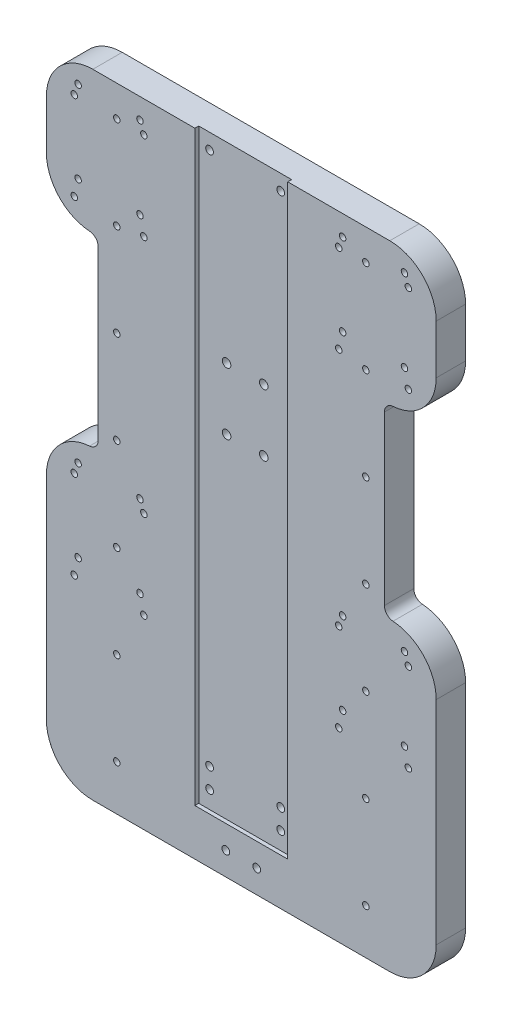
SolidWorks part; units mm, degrees
ref_plane "Piano frontale" through (0, 0, 0) normal (0, 0, 1) x (1, 0, 0)
ref_plane "Piano superiore" through (0, 0, 0) normal (0, 1, 0) x (1, 0, 0)
ref_plane "Piano destro" through (0, 0, 0) normal (1, 0, 0) x (0, 0, -1)
sketch "Schizzo1" plane through (0, 0, 0) normal (0, 0, 1) x (1, 0, 0)
  line L1 (126, -250) -> (-126, -250)
  line L2 (126, -250) -> (126, 250)
  line L3 (126, 250) -> (-126, 250)
  line L4 (-126, -250) -> (-126, 250)
  line L5 (126, -250) -> (-126, 250) construction
  line L6 (126, 250) -> (-126, -250) construction
  point P0 (0, 0)
  dimension "D1" = 252
  dimension "D2" = 500
extrude "Estrusione-Estrusione1" add sketch "Schizzo1" along normal blind 19
sketch "Schizzo2" plane through (0, 0, 19) normal (0, 0, 1) x (1, 0, 0)
  line L0 (1265.2426, 21.4119) -> (-695.7574, 21.4119) construction
  line L1 (1265.2426, 13.5541) -> (-695.7574, 13.5541) construction
  line L2 (1265.2426, 53.5541) -> (-695.7574, 53.5541) construction
  line L3 (1265.2426, 61.4119) -> (-695.7574, 61.4119) construction
  line L4 (-126, 250) -> (-126, -250)
  line L5 (-126, -250) -> (126, -250)
  line L6 (126, -250) -> (126, 250)
  line L7 (126, 250) -> (-126, 250)
  line L8 (-126, 250) -> (-126, -250) construction
  line L9 (-126, -250) -> (126, -250) construction
  line L10 (126, -250) -> (126, 250) construction
  line L11 (126, 250) -> (-126, 250) construction
  line L12 (1265.2426, 21.4119) -> (-695.7574, 21.4119) construction
  line L13 (1265.2426, 13.5541) -> (-695.7574, 13.5541) construction
  line L14 (1265.2426, 53.5541) -> (-695.7574, 53.5541) construction
  line L15 (1265.2426, 61.4119) -> (-695.7574, 61.4119) construction
  line L16 (126, -45.017) -> (-126, -45.017) construction
  line L17 (126, -25.017) -> (-126, -25.017) construction
  line L18 (126, -45.017) -> (-126, -45.017) construction
  line L19 (126, -25.017) -> (-126, -25.017) construction
  line L20 (-126, -45.017) -> (-126, -25.017) construction
  line L21 (126, -35.017) -> (-126, -35.017) construction
  line L22 (-126, -45.017) -> (126, -45.017) construction
  line L23 (-126, -45.017) -> (-126, -25.017) construction
  line L24 (-126, -25.017) -> (126, -25.017) construction
  line L25 (126, -45.017) -> (126, -25.017) construction
  circle A0 centre (110, 17.483) radius 3.9289
  circle A1 centre (110, 57.483) radius 3.9289
  circle A2 centre (-110, 17.483) radius 3.9289
  circle A3 centre (-110, 57.483) radius 3.9289
  circle A4 centre (110, -35.017) radius 3.5
  circle A5 centre (-110, -35.017) radius 3.5
  circle A6 centre (55, -35.017) radius 3.5
  circle A8 centre (-55, -35.017) radius 3.5
  circle A9 centre (20, -35.017) radius 3.5
  circle A10 centre (-20, -35.017) radius 3.5
  circle A11 centre (165, -35.017) radius 3.5 [skipped]
  dimension "D2" = 16
  dimension "D3" = 7.8579
  dimension "D4" = 16
  dimension "D5" = 7.8579
  dimension "D6" = 7
  dimension "D7" = 7
  dimension "D8" = 2
  dimension "D1" = 0
  dimension "D9" = 2
  dimension "D10" = 2
  dimension "D11" = 2
sketch "Schizzo3" plane through (0, 250, 0) normal (0, 1, 0) x (1, 0, 0)
  line L0 (126, -19) -> (-126, -19) construction
  line L1 (30, -16.5) -> (-30, -16.5)
  line L2 (30, -16.5) -> (30, -19)
  line L3 (30, -19) -> (-30, -19)
  line L4 (-30, -16.5) -> (-30, -19)
  line L5 (126, -19) -> (126, 0) construction
  line L6 (-126, -19) -> (-126, 0) construction
  line L7 (126, -19) -> (-126, -19) construction
  dimension "D1" = 2.5
  dimension "D2" = 96
  dimension "D3" = 96
extrude "Taglio-Estrusione1" cut sketch "Schizzo3" against normal through all
sketch "Schizzo4" plane through (0, 0, 16.5) normal (0, 0, 1) x (1, 0, 0)
  line L0 (30, -250) -> (30, 250) construction
  line L2 (30, 250) -> (-30, 250) construction
  line L3 (30, -250) -> (30, 250) construction
  line L6 (-30, 250) -> (-126, 250) construction
  line L7 (-30, -250) -> (-30, 250) construction
  point P11 (23, -118)
  point P14 (-23, -118)
  point P15 (-23, -105)
  point P16 (23, -105)
  point P17 (23, 240)
  point P18 (-23, 240)
  dimension "D1" = 46
  dimension "D2" = 13
  dimension "D3" = 13
  dimension "D4" = 46
  dimension "D5" = 7
  dimension "D6" = 345
  dimension "D7" = 10
  dimension "D8" = 46
  dimension "D9" = 7
  dimension "D10" = 10
  dimension "D11" = 7
  dimension "D12" = 7
sketch "Schizzo5" plane through (0, 0, 19) normal (0, 0, 1) x (1, 0, 0)
  point P4 (80.5006, 170)
  point P7 (80.5006, 110)
  point P16 (80.5006, 50)
  point P17 (80.5006, -10)
  point P18 (80.5006, -70)
  point P19 (80.5006, -130)
  point P20 (80.5006, 230)
hole_wizard "Tap Drill for M5 Tap2" positions "Sketch7" profile "Sketch8" hole size "M5" standard "ISO"
sketch "Sketch7" plane through (0, 0, 19) normal (0, 0, 1) x (1, 0, 0)
  point P0 (80.5006, -130)
  point P3 (80.5006, -70)
  point P7 (80.5006, -10)
  point P10 (80.5006, 50)
  point P13 (80.5006, 110)
  point P16 (80.5006, 170)
  point P19 (80.5006, 230)
sketch "Sketch8" plane through (80.5006, -130, 19) normal (1, 0, 0) x (0, -1, 0)
  line L0 (0, 0) -> (0, 37.8618)
  line L1 (0, 37.8618) -> (2.1, 36.6)
  line L2 (2.1, 36.6) -> (2.1, 0)
  line L5 (2.1, 0) -> (0, 0)
  line L10 (0, 37.8618) -> (-2.1, 36.6) construction
  line L11 (0, -6.35) -> (0, 107.95) construction
  dimension "Hole Dia." = 4.2
  dimension "Hole Depth" = 36.6
  dimension "Drill Angle" = 118
sketch "Schizzo6" plane through (0, 0, 19) normal (0, 0, 1) x (1, 0, 0)
  line L0 (126, -250) -> (126, 250) construction
  line L2 (126, 250) -> (30, 250) construction
  point P23 (108, 172.8083)
  point P26 (63, 172.8083)
  point P27 (63, 229.8083)
  point P28 (108, 229.8083)
  dimension "D1" = 45
  dimension "D2" = 45
  dimension "D3" = 57
  dimension "D4" = 57
  dimension "D5" = 18
  dimension "D6" = 20.1917
  dimension "D7" = 20.1917
  dimension "D8" = 18
hole_wizard "Tap Drill for M5 Tap1" positions "Sketch14" profile "Sketch15" hole size "M5" standard "ISO"
sketch "Sketch14" plane through (0, 0, 19) normal (0, 0, 1) x (1, 0, 0)
  line L1 (105.5, 183.8083) -> (65.5, 183.8083)
  line L2 (105.5, 183.8083) -> (105.5, 236.8083)
  line L3 (105.5, 236.8083) -> (65.5, 236.8083)
  line L4 (65.5, 183.8083) -> (65.5, 236.8083)
  line L6 (105.5, -28.1917) -> (65.5, -28.1917)
  line L7 (105.5, -28.1917) -> (105.5, 24.8083)
  line L8 (105.5, 24.8083) -> (65.5, 24.8083)
  line L9 (65.5, -28.1917) -> (65.5, 24.8083)
  line L10 (85.5, -28.1917) -> (85.5, 236.8083) construction
  line L12 (105.5, 210.3083) -> (65.5, 210.3083) construction
  line L14 (105.5, -1.6917) -> (65.5, -1.6917) construction
  line L16 (108, 172.8083) -> (63, 172.8083) construction
  line L18 (85.5, 256.2745) -> (85.5, -301.4126) construction
  point P0 (108, 172.8083)
  point P3 (108, 229.8083)
  point P6 (63, 229.8083)
  point P9 (63, 172.8083)
  point P12 (63, 17.8083)
  point P14 (63, -39.1917)
  point P16 (108, -39.1917)
  point P18 (108, 17.8083)
  point P19 (105.5, 236.8083)
  point P21 (65.5, 236.8083)
  point P23 (105.5, 183.8083)
  point P25 (65.5, 183.8083)
  point P99 (105.5, -28.1917)
  point P102 (65.5, -28.1917)
  point P105 (65.5, 24.8083)
  point P108 (105.5, 24.8083)
  point P138 (105.5, 183.8083)
  point P139 (65.5, 183.8083)
  point P140 (65.5, 236.8083)
  point P141 (105.5, 236.8083)
  point P142 (105.5, -28.1917)
  point P143 (65.5, -28.1917)
  point P144 (65.5, 24.8083)
  point P145 (105.5, 24.8083)
  dimension "D1" = 40
  dimension "D2" = 53
  dimension "D3" = 40
  dimension "D4" = 53
sketch "Sketch15" plane through (108, 172.8083, 19) normal (1, 0, 0) x (0, -1, 0)
  line L0 (0, 0) -> (0, 37.8618)
  line L1 (0, 37.8618) -> (2.1, 36.6)
  line L2 (2.1, 36.6) -> (2.1, 0)
  line L5 (2.1, 0) -> (0, 0)
  line L10 (0, 37.8618) -> (-2.1, 36.6) construction
  line L11 (0, -6.35) -> (0, 107.95) construction
  dimension "Hole Dia." = 4.2
  dimension "Hole Depth" = 36.6
  dimension "Drill Angle" = 118
hole_wizard "Tap Drill for M6 Tap4" positions "Sketch9" profile "Sketch10" hole size "M6" standard "ISO"
sketch "Sketch9" plane through (0, 0, 16.5) normal (0, 0, 1) x (1, 0, 0)
  point P0 (23, -118)
  point P3 (23, -105)
  point P6 (-23, -118)
  point P9 (-23, -105)
  point P12 (23, 240)
  point P15 (-23, 240)
sketch "Sketch10" plane through (23, -118, 16.5) normal (1, 0, 0) x (0, -1, 0)
  line L0 (0, 0) -> (0, 38.1022)
  line L1 (0, 38.1022) -> (2.5, 36.6)
  line L2 (2.5, 36.6) -> (2.5, 0)
  line L5 (2.5, 0) -> (0, 0)
  line L10 (0, 38.1022) -> (-2.5, 36.6) construction
  line L11 (0, -6.35) -> (0, 107.95) construction
  dimension "Hole Dia." = 5
  dimension "Hole Depth" = 36.6
  dimension "Drill Angle" = 118
sketch "Sketch11" plane through (0, 0, 16.5) normal (0, 0, 1) x (1, 0, 0)
  line L0 (0, -250) -> (0, 250) construction
  line L1 (30, -250) -> (-30, -250) construction
  line L2 (30, 250) -> (-30, 250) construction
ref_plane "Plane1" through (0, 0, 0) normal (-1, 0, 0) x (0, 0, 1)
mirror "Mirror1" about plane through (0, 0, 0) normal (-1, 0, 0) of "Tap Drill for M5 Tap2"
mirror "Mirror2" about plane through (0, 0, 0) normal (-1, 0, 0) of "Tap Drill for M5 Tap1"
sketch "Sketch16" plane through (0, 0, 0) normal (0, 0, -1) x (-1, 0, 0)
  line L0 (126, 250) -> (126, -250) construction
  line L1 (126, -317.9299) -> (-126, -317.9299)
  line L2 (126, -317.9299) -> (126, -159.25)
  line L3 (126, -159.25) -> (-126, -159.25)
  line L4 (-126, -317.9299) -> (-126, -159.25)
  line L5 (-126, -250) -> (-126, 250) construction
  line L9 (-12.9, -159.25) -> (25.2, -159.25) construction
extrude "Cut-Extrude1" cut sketch "Sketch16" against normal blind 28
sketch "Sketch26" plane through (0, 0, 16.5) normal (0, 0, 1) x (1, 0, 0)
  line L0 (30, -159.25) -> (30, 250) construction
  line L1 (-30, -159.25) -> (30, -159.25)
  line L2 (-30, -159.25) -> (-30, -129.25)
  line L3 (-30, -129.25) -> (30, -129.25)
  line L4 (30, -159.25) -> (30, -129.25)
  dimension "D1" = 30
extrude "Boss-Extrude1" add sketch "Sketch26" along normal up to surface (2.5 mm away) up to face at (-78, 45.375, 19)
hole_wizard "M5 Clearance Hole1" positions "Sketch17" profile "Sketch18" hole size "M5" standard "ISO" end condition through all
sketch "Sketch17" plane through (0, 0, 16.5) normal (0, 0, 1) x (1, 0, 0)
  line L0 (12, 86.3083) -> (-12, 126.3083) construction
  line L1 (-12, 126.3083) -> (-12, 86.3083) construction
  line L2 (-12, 86.3083) -> (12, 126.3083) construction
  line L3 (12, 126.3083) -> (12, 86.3083) construction
  line L4 (12, 86.3083) -> (-12, 86.3083) construction
  line L7 (-12, 126.3083) -> (12, 126.3083) construction
  point P0 (-12, 86.3083)
  point P2 (12, 86.3083)
  point P4 (12, 126.3083)
  point P6 (-12, 126.3083)
  dimension "D1" = 40
  dimension "D2" = 24
sketch "Sketch18" plane through (-12, 86.3083, 16.5) normal (1, 0, 0) x (0, -1, 0)
  line L0 (0, 0) -> (0, 16.5)
  line L1 (0, 16.5) -> (2.75, 16.5)
  line L2 (2.75, 16.5) -> (2.75, 0)
  line L5 (2.75, 0) -> (0, 0)
  line L11 (0, -6.35) -> (0, 107.95) construction
  dimension "Thru Hole Dia." = 5.5
  dimension "Thru Hole Depth" = 16.5
sketch "Sketch19" plane through (0, -195.45, 0) normal (0, -1, 0) x (-1, 0, 0)
  line L0 (0, -70.7) -> (0, 68.239) construction
  line L1 (126, -9.5) -> (-126, -9.5) construction
  line L2 (126, -19) -> (126, 0) construction
  line L3 (-126, -19) -> (-126, 0) construction
  line L5 (28.2, 0) -> (-28.2, 0) construction
  point P8 (20, -9.5)
  point P9 (-20, -9.5)
  point P12 (-20, 9.5)
  point P13 (20, 9.5)
  dimension "D1" = 20
hole_wizard "Tap Drill for M6 Tap2" positions "Sketch22" profile "Sketch23" hole size "M6" standard "ISO"
sketch "Sketch22" plane through (0, -159.25, 0) normal (0, -1, 0) x (-1, 0, 0)
  point P0 (20, -7.125)
  point P2 (-20, -7.125)
sketch "Sketch23" plane through (-20, -159.25, 7.125) normal (1, 0, 0) x (0, 0, -1)
  line L0 (0, 0) -> (0, 31.5022)
  line L1 (0, 31.5022) -> (2.5, 30)
  line L2 (2.5, 30) -> (2.5, 0)
  line L5 (2.5, 0) -> (0, 0)
  line L10 (0, 31.5022) -> (-2.5, 30) construction
  line L11 (0, -6.35) -> (0, 107.95) construction
  dimension "Hole Dia." = 5
  dimension "Hole Depth" = 30
  dimension "Drill Angle" = 118
hole_wizard "Tap Drill for M6 Tap3" positions "Sketch24" profile "Sketch25" hole size "M6" standard "ISO" end condition through all
sketch "Sketch24" plane through (0, 0, 0) normal (0, 0, -1) x (-1, 0, 0)
  point P0 (-10, -144.25)
  point P6 (10, -144.25)
sketch "Sketch25" plane through (10, -144.25, 0) normal (1, 0, 0) x (0, 1, 0)
  line L0 (0, 0) -> (0, 19)
  line L1 (0, 19) -> (2.5, 19)
  line L2 (2.5, 19) -> (2.5, 0)
  line L5 (2.5, 0) -> (0, 0)
  line L11 (0, -6.35) -> (0, 107.95) construction
  dimension "Thru Hole Dia." = 5
  dimension "Thru Hole Depth" = 19
sketch "Sketch27" plane through (0, 0, 19) normal (0, 0, 1) x (1, 0, 0)
  line L2 (-126, 38.082) -> (-126, 158.222)
  line L4 (-92.5, 38.082) -> (-92.5, 158.222)
  line L5 (-126, 38.082) -> (-92.5, 38.082)
  line L7 (-126, 158.222) -> (-92.5, 158.222)
  line L9 (-92.5, 40.082) -> (-92.5, 156.222) construction
  line L10 (-126, 40.082) -> (-126, 156.222) construction
  line L11 (-128, 158.222) -> (-90.5, 158.222) construction
  line L12 (-128, 38.082) -> (-128, 158.222) construction
  line L13 (-128, 38.082) -> (-90.5, 38.082) construction
  line L14 (-126, 40.082) -> (-92.5, 40.082) construction
  line L15 (-90.5, 38.082) -> (-90.5, 158.222) construction
  line L16 (-126, 156.222) -> (-92.5, 156.222) construction
  line L17 (-126, 98.152) -> (126, 98.152) construction
  line L18 (126, -159.25) -> (126, 250) construction
  line L19 (126, 98.152) -> (0, 98.152) construction
  line L20 (0, 98.152) -> (0, 87.9155) construction
  line L21 (-126, 38.082) -> (-92.5, 38.082)
  line L22 (-126, 158.222) -> (-92.5, 158.222)
  line L23 (126, 158.222) -> (92.5, 158.222)
  line L24 (126, 38.082) -> (92.5, 38.082)
  line L25 (126, 158.222) -> (92.5, 158.222)
  line L26 (126, 38.082) -> (92.5, 38.082)
  line L27 (92.5, 38.082) -> (92.5, 158.222)
  line L28 (126, 38.082) -> (126, 158.222)
  dimension "D1" = 2
extrude "Cut-Extrude2" cut sketch "Sketch27" against normal blind 76.9911 contours L27 L24 L23 | L7 L5 L4 region at (-109.25, 98.152, 19) region at (109.25, 98.152, 19)
fillet "Fillet1" radius 30 4 edges at (126, 158.222, 9.5) (126, 38.082, 9.5) (-126, 158.222, 9.5) (-126, 38.082, 9.5)
fillet "Fillet2" radius 30 4 edges at (126, 250, 9.5) (-126, 250, 9.5) (-126, -159.25, 9.5) (126, -159.25, 9.5)
fillet "Fillet3" radius 6 4 edges at (92.5, 158.222, 9.5) (92.5, 38.082, 9.5) (-92.5, 38.082, 9.5) (-92.5, 158.222, 9.5)
equation "\"D3@Schizzo3\"=\"D2@Schizzo3\""
equation "\"D11@Schizzo4\"=\"D5@Schizzo4\""
